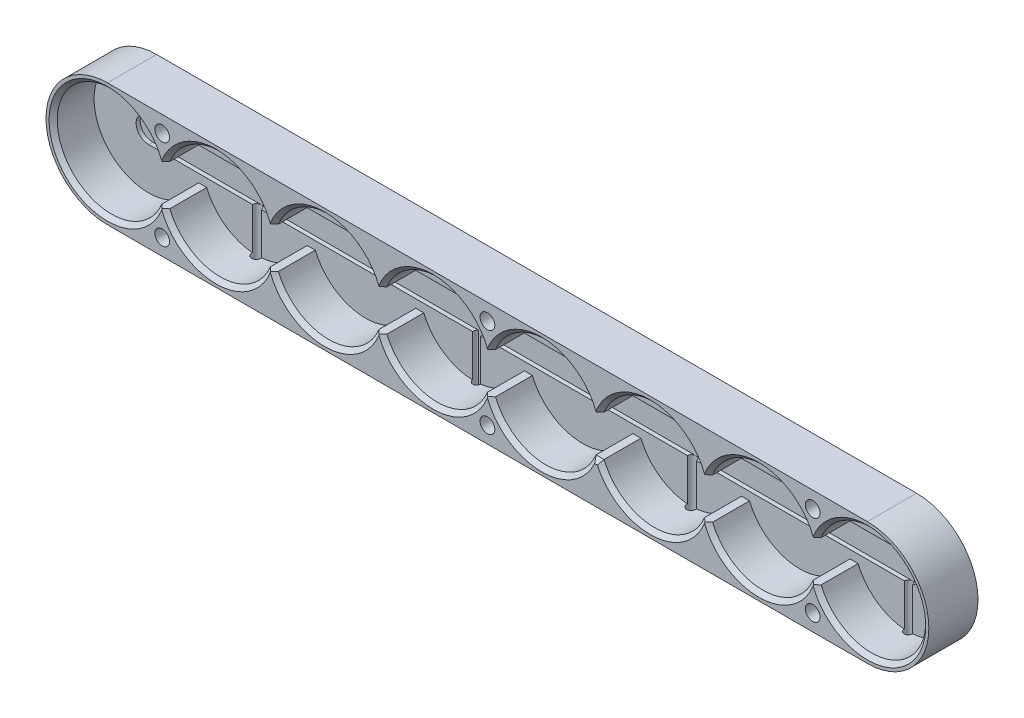
SolidWorks part; units mm, degrees
ref_plane "Front Plane" through (0, 0, 0) normal (0, 0, 1) x (1, 0, 0)
ref_plane "Top Plane" through (0, 0, 0) normal (0, 1, 0) x (1, 0, 0)
ref_plane "Right Plane" through (0, 0, 0) normal (1, 0, 0) x (0, 0, -1)
sketch "Sketch1" plane through (0, 0, 0) normal (0, 0, 1) x (1, 0, 0)
  line L0 (0, 0) -> (185.5, 0)
  line L1 (0, 15) -> (185.5, 15)
  line L2 (0, -15) -> (185.5, -15)
  line L3 (0, 5) -> (186.9, 5)
  line L4 (0, -5) -> (186.9, -5)
  circle A0 centre (0, 0) radius 13.25
  circle A1 centre (26.5, 0) radius 13.25
  circle A2 centre (53, 0) radius 13.25
  circle A3 centre (79.5, 0) radius 13.25
  circle A4 centre (106, 0) radius 13.25
  circle A5 centre (132.5, 0) radius 13.25
  circle A6 centre (159, 0) radius 13.25
  circle A7 centre (185.5, 0) radius 13.25
  arc A8 (0, 15) -> (0, -15) centre (0, 0) ccw
  arc A9 (185.5, -15) -> (185.5, 15) centre (185.5, 0) ccw
  dimension "D1" = 8
  dimension "D2" = 5
  dimension "D4" = 26.5
  dimension "D5" = 26.5
  dimension "D3" = 5
extrude "Boss-Extrude1" add sketch "Sketch1" along normal blind 10 contours L2 A9 L1 A8 A7 L4 A6 A5 A4 A3 A2 A1 A0 L3
sketch "Sketch2" plane through (0, 0, 0) normal (0, 0, -1) x (-1, 0, 0)
  line L0 (0, -15) -> (-185.5, -15) construction
  line L1 (0, 15) -> (-185.5, 15) construction
  line L2 (0, -15) -> (-185.5, -15)
  line L3 (0, 15) -> (-185.5, 15)
  arc A0 (-185.5, 15) -> (-185.5, -15) centre (-185.5, 0) ccw construction
  arc A1 (0, -15) -> (0, 15) centre (0, 0) ccw construction
  arc A2 (-185.5, 15) -> (-185.5, -15) centre (-185.5, 0) ccw
  arc A3 (0, -15) -> (0, 15) centre (0, 0) ccw
extrude "Boss-Extrude2" add sketch "Sketch2" along normal blind 2
chamfer "Chamfer4" distance 1 angle 45 15 edges at (-13.25, 0, 10) (26.5, 13.25, 10) (26.5, -13.25, 10) (53, 13.25, 10) (53, -13.25, 10) (79.5, 13.25, 10) (79.5, -13.25, 10) (106, 13.25, 10) (132.5, 13.25, 10) (159, 13.25, 10) (159, -13.25, 10) (198.75, 0, 10) (106, -13.25, 10) (132.5, -13.25, 10) (119.25, -5, 10)
sketch "Sketch4" plane through (0, 0, -2) normal (0, 0, -1) x (-1, 0, 0)
  line L0 (-186.9, -3) -> (-180.9, -3)
  line L1 (-186.9, 3) -> (-180.9, 3)
  line L2 (-192.9, -3) -> (-186.9, -3)
  line L3 (-192.9, 3) -> (-186.9, 3)
  line L5 (-92.75, -18.8272) -> (-92.75, 15) construction
  line L6 (0, 15) -> (-185.5, 15) construction
  line L7 (7.4, 3) -> (1.4, 3)
  line L8 (7.4, -3) -> (1.4, -3)
  line L9 (1.4, 3) -> (-4.6, 3)
  line L10 (1.4, -3) -> (-4.6, -3)
  arc A1 (-180.9, -3) -> (-180.9, 3) centre (-180.9, 0) ccw
  arc A2 (-192.9, 3) -> (-192.9, -3) centre (-192.9, 0) ccw
  arc A3 (7.4, 3) -> (7.4, -3) centre (7.4, 0) cw
  arc A4 (-4.6, -3) -> (-4.6, 3) centre (-4.6, 0) cw
sketch "Sketch5" plane through (0, 0, 10) normal (0, 0, 1) x (1, 0, 0)
  line L0 (0, 0) -> (185.5, 0) construction
  circle A0 centre (13.35, 11) radius 1.8
  circle A1 centre (92.75, 11) radius 1.8
  circle A2 centre (172.15, 11) radius 1.8
  circle A3 centre (92.75, -11) radius 1.8
  circle A4 centre (172.15, -11) radius 1.8
  circle A5 centre (13.35, -11) radius 1.8
  point P4 (13.25, 5.244)
  dimension "D1" = 3.6
  dimension "D5" = 79.4
  dimension "12" = 11
  dimension "D4" = 79.4
  dimension "D2" = 3
  dimension "D3" = 2
extrude "Cut-Extrude2" cut sketch "Sketch5" against normal blind 12
sketch "Sketch6" plane through (0, 0, -2) normal (0, 0, -1) x (-1, 0, 0)
  circle A0 centre (-13.35, 11) radius 2.9
  circle A1 centre (-92.75, 11) radius 2.9
  circle A2 centre (-172.15, 11) radius 2.9
  circle A3 centre (-92.75, -11) radius 2.9
  circle A4 centre (-172.15, -11) radius 2.9
  circle A5 centre (-13.35, -11) radius 2.9
  dimension "D1" = 3
  dimension "D3" = 79.4
  dimension "D2" = 2
extrude "Cut-Extrude3" cut sketch "Sketch6" against normal blind 4.5
chamfer "Chamfer5" distance 1.1 angle 45 6 edges at (10.45, -11, 2.5) (169.25, 11, 2.5) (169.25, -11, 2.5) (89.85, -11, 2.5) (89.85, 11, 2.5) (10.45, 11, 2.5)
sketch "Sketch7" plane through (0, 0, -2) normal (0, 0, -1) x (-1, 0, 0)
  line L0 (0, 0) -> (0, 4.1725) construction
sketch "Sketch9" plane through (0, 0, 0) normal (0, 0, 1) x (1, 0, 0)
  line L4 (185.5, 3) -> (0.0868, 3)
  line L5 (0.0868, -3) -> (185.5, -3)
  arc A0 (0.0868, 3) -> (0.0868, -3) centre (0, 0) ccw
  arc A1 (185.5, -3) -> (185.5, 3) centre (185.5, 0) ccw
extrude "Cut-Extrude6" cut sketch "Sketch9" against normal blind 1
sketch "Sketch10" plane through (0, -15, 0) normal (0, -1, 0) x (1, 0, 0)
  line L0 (39.75, 10) -> (13.25, 10) construction
  line L1 (39.75, 10) -> (13.25, 10)
  line L2 (185.5, 10) -> (185.5, -2) construction
  line L4 (0.0868, -1) -> (185.5, -1) construction
  line L6 (145.75, 10) -> (119.5747, 10) construction
  line L7 (92.75, 10) -> (66.25, 10) construction
  line L8 (92.75, 10) -> (66.25, 10)
  line L9 (145.75, 10) -> (119.5747, 10)
  line L10 (0.0868, -1) -> (185.5, -1)
  circle A4 centre (132.6624, 0.1284) radius 1.1284
  circle A6 centre (26.5, 0.1284) radius 1.1284
  circle A7 centre (79.5812, 0.1284) radius 1.1284
  circle A8 centre (80.1003, -0.1277) radius 1
  circle A9 centre (185.5, 0) radius 1
  point P6 (132.6624, 0.1284)
  point P13 (79.5, 10)
  point P20 (132.6624, 10)
  point P22 (26.5, 10)
  line M4 (185.5, -2) -> (185.5, 10)
  dimension "D1" = 3
extrude "Cut-Extrude9" cut sketch "Sketch10" against normal blind 13 contours A6 | A8 | A4 | A9 M4
